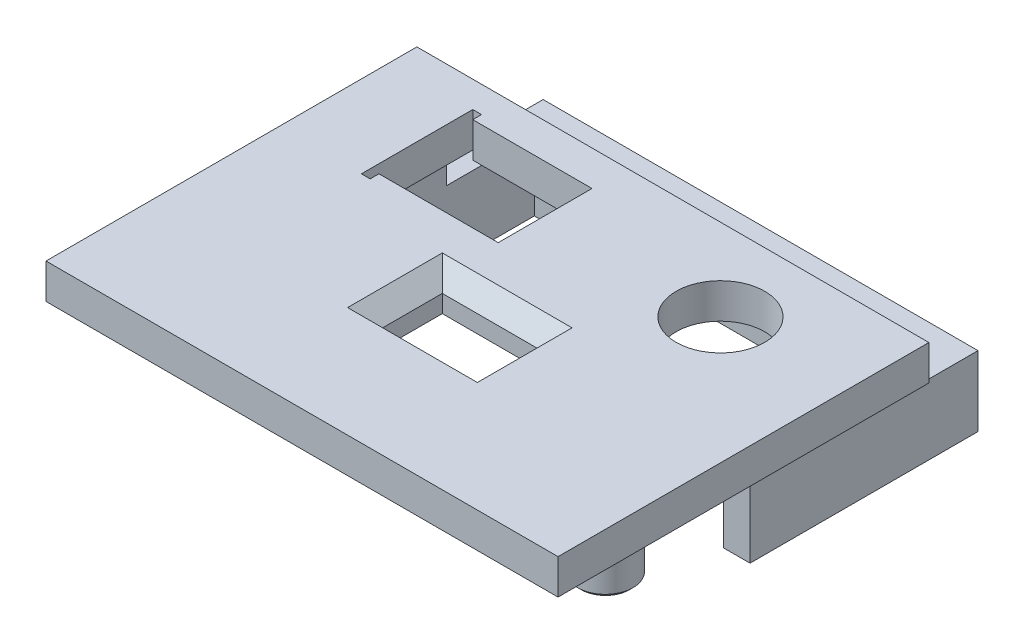
SolidWorks part; units mm, degrees
ref_plane "Front Plane" through (0, 0, 0) normal (0, 0, 1) x (1, 0, 0)
ref_plane "Top Plane" through (0, 0, 0) normal (0, 1, 0) x (1, 0, 0)
ref_plane "Right Plane" through (0, 0, 0) normal (1, 0, 0) x (0, 0, -1)
sketch "Parts" plane through (0, 0, 0) normal (0, 1, 0) x (1, 0, 0)
  line L0 (-9.9, 2.7) -> (-7.9, 2.7) construction
  line L1 (-7.9, 5.4) -> (7.9, 5.4) construction
  line L2 (-7.9, 5.4) -> (-7.9, 2.7) construction
  line L3 (-7.9, -5.4) -> (7.9, -5.4) construction
  line L4 (7.9, 5.4) -> (7.9, 2.7) construction
  line L5 (-7.9, 5.4) -> (7.9, -5.4) construction
  line L6 (-7.9, -5.4) -> (7.9, 5.4) construction
  line L7 (-9.9, -2.7) -> (-7.9, -2.7) construction
  line L8 (9.9, 2.7) -> (7.9, 2.7) construction
  line L9 (9.9, -2.7) -> (7.9, -2.7) construction
  line L10 (-7.9, -2.7) -> (-7.9, -5.4) construction
  line L11 (7.9, -2.7) -> (7.9, -5.4) construction
  line L12 (-9.9125, 9.075) -> (9.9125, 9.075) construction
  line L13 (-2.2, 2.8) -> (2.2, 2.8) construction
  line L14 (-2.2, 2.8) -> (-2.2, 0.4) construction
  line L15 (-2.2, 0.4) -> (2.2, 0.4) construction
  line L16 (2.2, 2.8) -> (2.2, 0.4) construction
  line L17 (-2.2, 2.8) -> (2.2, 0.4) construction
  line L18 (-2.2, 0.4) -> (2.2, 2.8) construction
  line L19 (-9.9125, 11.75) -> (-2.6125, 11.75) construction
  line L21 (-9.9125, 6.4) -> (-2.6125, 6.4) construction
  line L22 (-2.6125, 11.75) -> (-2.6125, 6.4) construction
  line L23 (-9.9125, 11.75) -> (-2.6125, 6.4) construction
  line L24 (-9.9125, 6.4) -> (-2.6125, 11.75) construction
  line L26 (-9.9125, 6.4) -> (-9.9125, 11.75) construction
  line L29 (-2.6125, 11.75) -> (1.3875, 11.75) construction
  line L31 (-2.6125, 6.4) -> (1.3875, 6.4) construction
  line L32 (1.3875, 11.75) -> (1.3875, 6.4) construction
  line L33 (-14.6, -7.4) -> (14.6, -7.4)
  line L34 (-14.6, -7.4) -> (-14.6, 13.75)
  line L35 (-14.6, 13.75) -> (14.6, 13.75)
  line L36 (14.6, -7.4) -> (14.6, 13.75)
  line L37 (0, 9.075) -> (0, 5.4) construction
  line L38 (-2.6125, 11.75) -> (-2.6125, 12.25) construction
  line L39 (-2.6125, 12.25) -> (1.3875, 12.25) construction
  line L40 (1.3875, 12.25) -> (1.3875, 11.75) construction
  line L41 (-2.6125, 6.4) -> (-2.6125, 5.9) construction
  line L42 (-2.6125, 5.9) -> (1.3875, 5.9) construction
  line L43 (1.3875, 5.9) -> (1.3875, 6.4) construction
  line L44 (-12.6, 0) -> (-14.6, 0) construction
  line L45 (12.6, 0) -> (14.6, 0) construction
  line L46 (-9.4125, 11.75) -> (-9.4125, 12.25) construction
  line L47 (-9.4125, 12.25) -> (-9.9125, 12.25) construction
  line L48 (-9.9125, 12.25) -> (-9.9125, 11.75) construction
  line L49 (-9.9125, 6.4) -> (-9.9125, 5.9) construction
  line L50 (-9.9125, 5.9) -> (-9.4125, 5.9) construction
  line L51 (-9.4125, 5.9) -> (-9.4125, 6.4) construction
  arc A0 (-9.9, 2.7) -> (-9.9, -2.7) centre (-9.9, 0) ccw construction
  arc A1 (9.9, -2.7) -> (9.9, 2.7) centre (9.9, 0) ccw construction
  circle A2 centre (-9.9, 0) radius 1.575 construction
  circle A3 centre (9.9, 0) radius 1.575 construction
  circle A4 centre (7.3875, 9.075) radius 2.525 construction
  point P0 (0, 0)
  point P16 (0, 1.6)
  point P23 (-6.2625, 9.075)
  dimension "D3" = 5.4
  dimension "D4" = 5.4
  dimension "D5" = 3.15
  dimension "D6" = 3.15
  dimension "D14" = 5.05
  dimension "D1" = 10.8
  dimension "D2" = 15.8
  dimension "D7" = 2.4
  dimension "D8" = 4.4
  dimension "D9" = 5.8
  dimension "D10" = 7.3
  dimension "D11" = 4
  dimension "D12" = 5.35
  dimension "D13" = 1
  dimension "D15" = 2
  dimension "D16" = 2
  dimension "D17" = 2
  dimension "D18" = 6
  dimension "D19" = 0.5
  dimension "D20" = 0.5
  dimension "D21" = 2
  dimension "D22" = 0.5
  dimension "D23" = 0.5
extrude "Main Face" add sketch "Parts" against normal blind 2
sketch "Sketch3" plane through (0, 0, 0) normal (0, 1, 0) x (1, 0, 0)
  line L0 (-2.6125, 11.75) -> (-2.6125, 6.4) construction
  line L1 (-9.9125, 11.75) -> (-2.6125, 11.75) construction
  line L2 (-9.9125, 6.4) -> (-9.9125, 11.75) construction
  line L3 (-9.9125, 6.4) -> (-2.6125, 6.4) construction
  line L4 (-2.6125, 11.75) -> (-2.6125, 6.4)
  line L5 (-9.4125, 11.75) -> (-2.6125, 11.75)
  line L6 (-9.9125, 6.4) -> (-9.9125, 11.75)
  line L7 (-9.4125, 6.4) -> (-2.6125, 6.4)
  line L8 (-9.9125, 6.4) -> (-9.9125, 5.9) construction
  line L9 (-9.4125, 5.9) -> (-9.4125, 6.4) construction
  line L10 (-9.9125, 5.9) -> (-9.4125, 5.9) construction
  line L11 (-9.4125, 11.75) -> (-9.4125, 12.25) construction
  line L12 (-9.4125, 12.25) -> (-9.9125, 12.25) construction
  line L13 (-9.9125, 12.25) -> (-9.9125, 11.75) construction
  line L14 (-9.9125, 6.4) -> (-9.9125, 5.9)
  line L15 (-9.4125, 5.9) -> (-9.4125, 6.4)
  line L16 (-9.9125, 5.9) -> (-9.4125, 5.9)
  line L17 (-9.4125, 11.75) -> (-9.4125, 12.25)
  line L18 (-9.4125, 12.25) -> (-9.9125, 12.25)
  line L19 (-9.9125, 12.25) -> (-9.9125, 11.75)
  circle A0 centre (7.3875, 9.075) radius 2.525 construction
  circle A1 centre (7.3875, 9.075) radius 2.525
extrude "IR Cut" cut sketch "Sketch3" against normal blind 2
sketch "Sketch5" plane through (0, -2, 0) normal (0, -1, 0) x (1, 0, 0)
  line L0 (-2.6125, -11.75) -> (-2.6125, -6.4) construction
  line L2 (1.3875, -11.75) -> (1.3875, -6.4) construction
  line L4 (-2.6125, -11.75) -> (-2.6125, -6.4)
  line L6 (1.3875, -11.75) -> (1.3875, -6.4)
  line L8 (1.3875, -5.9) -> (1.3875, -6.4) construction
  line L9 (-2.6125, -5.9) -> (1.3875, -5.9) construction
  line L10 (-2.6125, -6.4) -> (-2.6125, -5.9) construction
  line L11 (1.3875, -12.25) -> (1.3875, -11.75) construction
  line L12 (-2.6125, -12.25) -> (1.3875, -12.25) construction
  line L13 (-2.6125, -11.75) -> (-2.6125, -12.25) construction
  line L14 (1.3875, -5.9) -> (1.3875, -6.4)
  line L15 (-2.6125, -5.9) -> (1.3875, -5.9)
  line L16 (-2.6125, -6.4) -> (-2.6125, -5.9)
  line L17 (1.3875, -12.25) -> (1.3875, -11.75)
  line L18 (-2.6125, -12.25) -> (1.3875, -12.25)
  line L19 (-2.6125, -11.75) -> (-2.6125, -12.25)
extrude "TSOP Groove" cut sketch "Sketch5" against normal blind 1.5
sketch "Sketch4" plane through (0, 0, 0) normal (0, 1, 0) x (1, 0, 0)
  line L14 (-2.7, -0.1) -> (2.7, -0.1)
  line L15 (2.7, -0.1) -> (2.7, 3.3)
  line L16 (2.7, 3.3) -> (-2.7, 3.3)
  line L17 (-2.7, 3.3) -> (-2.7, -0.1)
  line L18 (-2.7, -0.1) -> (2.7, -0.1)
  line L19 (2.7, -0.1) -> (2.7, 3.3)
  line L20 (2.7, 3.3) -> (-2.7, 3.3)
  line L21 (-2.7, 3.3) -> (-2.7, -0.1)
  dimension "D1" = 0.5
extrude "TOF Cut" cut sketch "Sketch4" against normal blind 2
sketch "Sketch6" plane through (0, -2, 0) normal (0, -1, 0) x (1, 0, 0)
  circle A0 centre (-9.9, 0) radius 1.575 construction
  circle A1 centre (9.9, 0) radius 1.575 construction
  circle A6 centre (-9.9, 0) radius 1.575
  circle A9 centre (9.9, 0) radius 1.575
extrude "Shafts" add sketch "Sketch6" along normal blind 5
chamfer "Chamfer1" distance 0.2 angle 45 2 edges at (9.9, -7, -1.575) (-9.9, -7, -1.575)
sketch "Sketch7" plane through (0, -2, 0) normal (0, -1, 0) x (1, 0, 0)
  line L1 (-7.5, 4.9) -> (7.5, 4.9)
  line L2 (-7.5, 4.9) -> (-7.5, 1.4)
  line L3 (-7.5, 1.4) -> (7.5, 1.4)
  line L4 (7.5, 4.9) -> (7.5, 1.4)
  line L5 (-7.5, 4.9) -> (7.5, 1.4) construction
  line L6 (-7.5, 1.4) -> (7.5, 4.9) construction
  line L7 (-7.9, 5.4) -> (7.9, 5.4) construction
  point P0 (0, 3.15)
  dimension "D1" = 3.5
  dimension "D2" = 15
  dimension "D3" = 0.5
extrude "PinSlots" cut sketch "Sketch7" against normal blind 1
chamfer "ToFWindow" distance 1 angle 45 4 edges at (2.7, 0, -1.6) (0, 0, 0.1) (-2.7, 0, -1.6) (0, 0, -3.3)
sketch "Sketch8" plane through (0, -2, 0) normal (0, -1, 0) x (1, 0, 0)
  line L1 (-12.4, -5.75) -> (-10.9, -5.75)
  line L2 (-12.4, -5.75) -> (-12.4, -11.75)
  line L3 (-12.4, -11.75) -> (-10.9, -11.75)
  line L4 (-10.9, -5.75) -> (-10.9, -11.75)
  line L5 (-12.4, -5.75) -> (-10.9, -11.75) construction
  line L6 (-12.4, -11.75) -> (-10.9, -5.75) construction
  line L10 (-14.6, 7.4) -> (-14.6, -13.75) construction
  line L11 (-14.6, -13.75) -> (14.6, -13.75) construction
  line L12 (0, -3.85) -> (0, 3.85) construction
  line L13 (12.4, -11.75) -> (10.9, -11.75)
  line L14 (10.9, -5.75) -> (10.9, -11.75)
  line L15 (12.4, -5.75) -> (10.9, -5.75)
  line L16 (12.4, -5.75) -> (12.4, -11.75)
  point P0 (-11.65, -8.75)
  dimension "D1" = 2.2
  dimension "D2" = 6
  dimension "D3" = 1.5
  dimension "D4" = 2
extrude "Boss-Extrude1" add sketch "Sketch8" along normal blind 6
sketch "Sketch14" plane through (0, 0, -11.75) normal (0, 0, -1) x (-1, 0, 0)
  line L5 (-10.9, -8) -> (-10.9, -2) construction
  line L6 (-10.9, -4) -> (-12.4, -4)
  line L7 (-10.9, -4) -> (-10.9, -8)
  line L8 (-10.9, -8) -> (-12.4, -8)
  line L9 (-12.4, -4) -> (-12.4, -8)
  line L10 (10.9, -8) -> (10.9, -2) construction
  line L11 (10.9, -4) -> (12.4, -4)
  line L12 (10.9, -4) -> (10.9, -8)
  line L13 (10.9, -8) -> (12.4, -8)
  line L14 (12.4, -4) -> (12.4, -8)
  dimension "D1" = 4
  dimension "D2" = 4
extrude "Boss-Extrude4" add sketch "Sketch14" along normal blind 5
sketch "Sketch15" plane through (0, 0, -16.75) normal (0, 0, -1) x (-1, 0, 0)
  line L0 (12.4, -8) -> (12.4, -4) construction
  line L1 (-12.4, -4) -> (12.4, -4)
  line L2 (-12.4, -4) -> (-12.4, -8)
  line L3 (-12.4, -8) -> (12.4, -8)
  line L4 (12.4, -4) -> (12.4, -8)
  dimension "D1" = 4
extrude "Boss-Extrude5" add sketch "Sketch15" along normal blind 2
sketch "Sketch16" plane through (0, 0, -16.75) normal (0, 0, 1) x (1, 0, 0)
  line L0 (0, 0) -> (0, -8) construction
  line L1 (10.9, -8) -> (-10.9, -8) construction
  line L3 (-4.5, -6) -> (-4.5, -4) construction
  line L4 (-10.9, -4) -> (10.9, -4) construction
  line L5 (-4.5, -6) -> (-4.5, -8) construction
  circle A0 centre (-4.5, -6) radius 1
  circle A1 centre (-1.5, -6) radius 1
  circle A2 centre (1.5, -6) radius 1
  circle A3 centre (4.5, -6) radius 1
  dimension "D1" = 2
  dimension "D2" = 3
  dimension "D3" = 1.5
extrude "Cut-Extrude4" cut sketch "Sketch16" against normal up to next
sketch "Sketch17" plane through (0, 0, -18.75) normal (0, 0, -1) x (-1, 0, 0)
  line L0 (-5, -6.866) -> (-5, -8)
  line L1 (-12.4, -8) -> (12.4, -8) construction
  line L2 (-5, -8) -> (-4, -8)
  line L3 (-4, -8) -> (-4, -6.866)
  line L4 (-4.5, -6) -> (-4.5, -8) construction
  line L5 (-1, -8) -> (-1, -6.866)
  line L6 (-2, -8) -> (-1, -8)
  line L7 (-2, -6.866) -> (-2, -8)
  line L8 (2, -8) -> (2, -6.866)
  line L9 (1, -8) -> (2, -8)
  line L10 (1, -6.866) -> (1, -8)
  line L11 (5, -8) -> (5, -6.866)
  line L12 (4, -8) -> (5, -8)
  line L13 (4, -6.866) -> (4, -8)
  circle A0 centre (-4.5, -6) radius 1 construction
  circle A1 centre (-4.5, -6) radius 1 construction
  arc A2 (-5, -6.866) -> (-4, -6.866) centre (-4.5, -6) ccw
  arc A3 (-2, -6.866) -> (-1, -6.866) centre (-1.5, -6) ccw
  arc A4 (1, -6.866) -> (2, -6.866) centre (1.5, -6) ccw
  arc A5 (4, -6.866) -> (5, -6.866) centre (4.5, -6) ccw
  circle A6 centre (4.5, -6) radius 1 construction
  dimension "D1" = 2
  dimension "D4" = 0.5
  dimension "D2" = 1
  dimension "D3" = 4
extrude "Cut-Extrude5" cut sketch "Sketch17" against normal blind 0.5
fillet "Fillet1" radius 0.5 8 edges at (-5, -7.433, -18.25) (-4, -7.433, -18.25) (-2, -7.433, -18.25) (-1, -7.433, -18.25) (1, -7.433, -18.25) (2, -7.433, -18.25) (4, -7.433, -18.25) (5, -7.433, -18.25)
